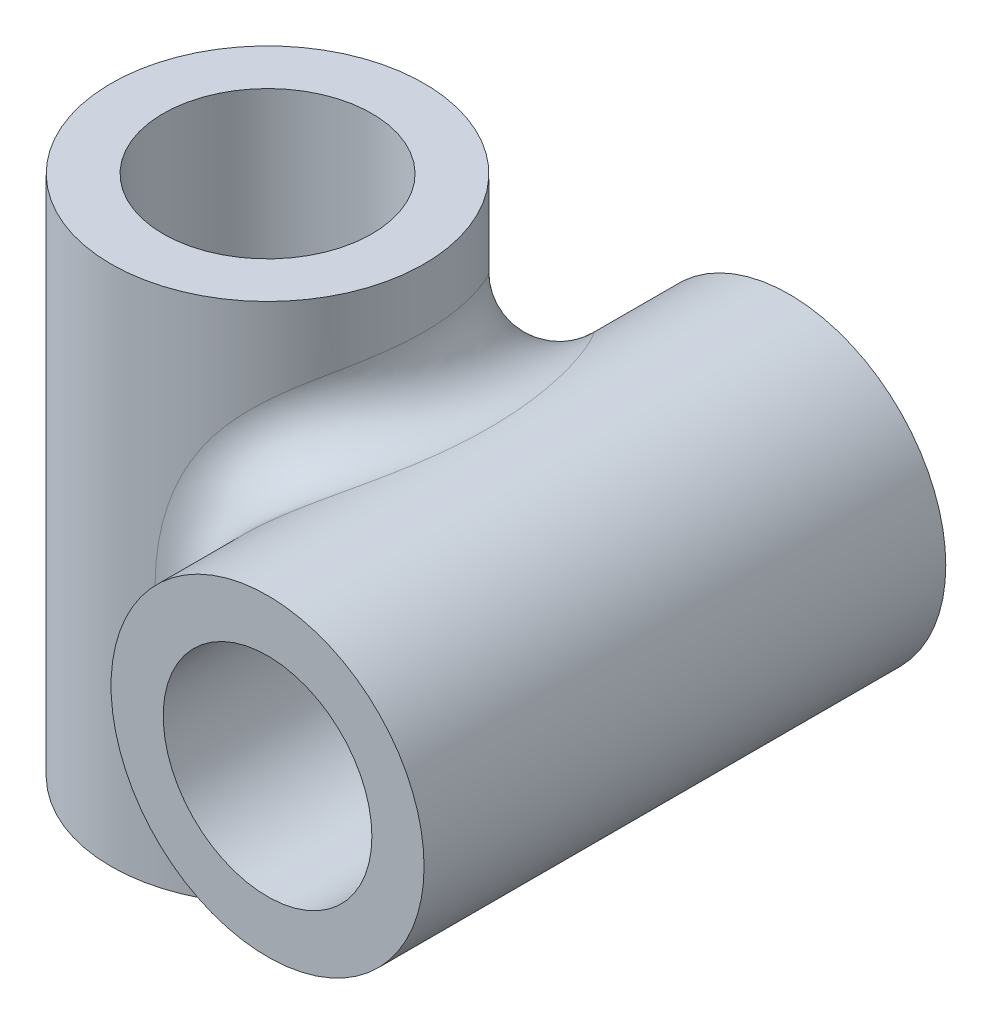
SolidWorks part; units mm, degrees
ref_plane "Front Plane" through (0, 0, 0) normal (0, 0, 1) x (1, 0, 0)
ref_plane "Top Plane" through (0, 0, 0) normal (0, 1, 0) x (1, 0, 0)
ref_plane "Right Plane" through (0, 0, 0) normal (1, 0, 0) x (0, 0, -1)
sketch "Sketch1" plane through (0, 0, 0) normal (0, 1, 0) x (1, 0, 0)
  circle A0 centre (0, 0) radius 2
  circle A1 centre (0, 0) radius 3
extrude "Boss-Extrude2" add sketch "Sketch1" along normal mid plane 10
sketch "Sketch3" plane through (0, 0, 0) normal (0, 0, 1) x (1, 0, 0)
  line L0 (3, -5) -> (3, 5) construction
  circle A0 centre (5, 0) radius 2
  circle A1 centre (5, 0) radius 3
extrude "Boss-Extrude3" add sketch "Sketch3" along normal mid plane 10
fillet "Fillet1" radius 1 1 edges at (2.0132, 0.2808, -2.2242)
